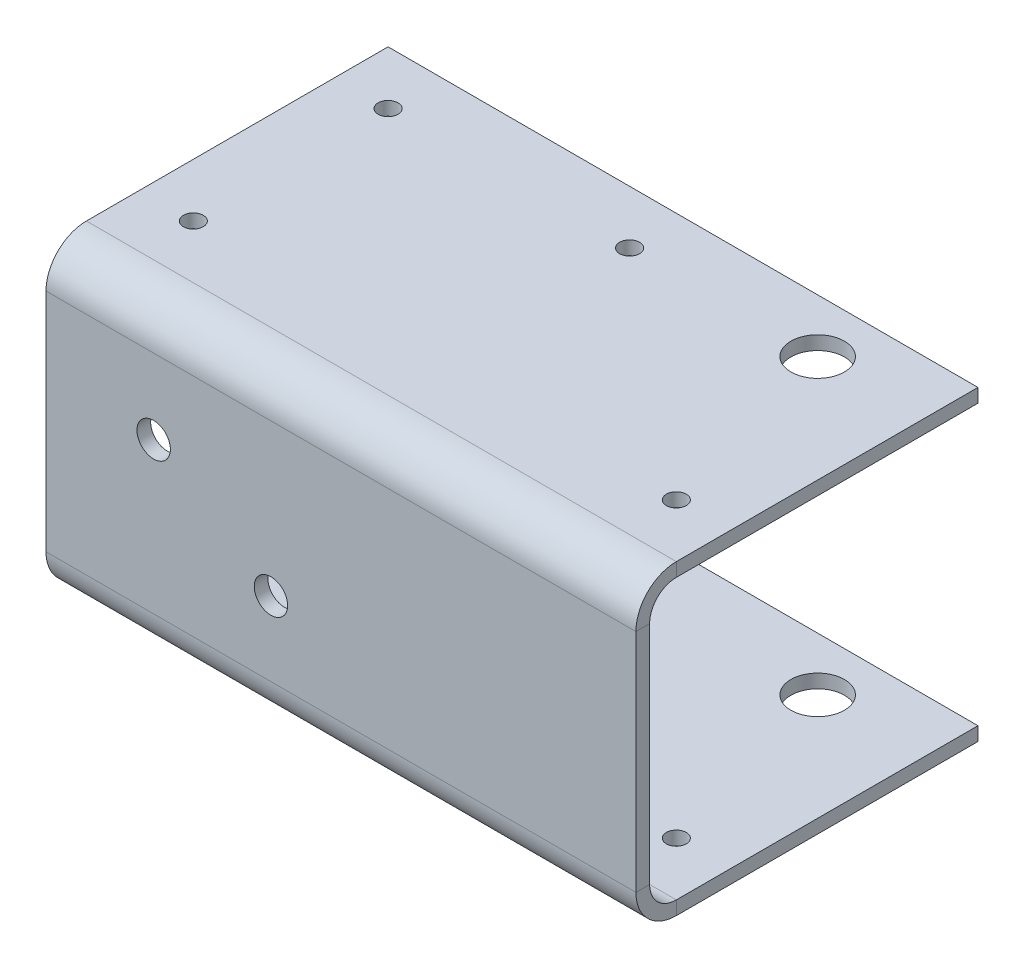
SolidWorks part; units mm, degrees
note: The reader was unsure of these and kept them because the rebuilt part matched: flange length of "Edge-Flange1".
material "6061-T6 (SS)"
ref_plane "Front Plane" through (0, 0, 0) normal (0, 0, 1) x (1, 0, 0)
ref_plane "Top Plane" through (0, 0, 0) normal (0, 1, 0) x (1, 0, 0)
ref_plane "Right Plane" through (0, 0, 0) normal (1, 0, 0) x (0, 0, -1)
sketch "Sketch1" plane through (0, 0, 0) normal (0, 0, 1) x (1, 0, 0)
  line L0 (-23.045, -12.8172) -> (5.6472, -12.8172) construction
  line L1 (5.6472, -12.8172) -> (11.9972, -12.8172) construction
  line L2 (11.9972, 3.7728) -> (11.9972, -12.8172) construction
  line L3 (5.6472, 3.7728) -> (11.9972, 3.7728) construction
  line L4 (-23.045, 3.7728) -> (5.6472, 3.7728) construction
  line L5 (-23.045, -12.8172) -> (-23.045, 3.7728) construction
  line L7 (-23.045, -12.8172) -> (5.6472, -12.8172)
  line L9 (5.6472, -12.8172) -> (11.9972, -12.8172)
  line L10 (11.9972, 3.7728) -> (11.9972, -12.8172)
  line L13 (5.6472, 3.7728) -> (11.9972, 3.7728)
  line L14 (-23.045, 3.7728) -> (5.6472, 3.7728)
  line L15 (-23.045, -12.8172) -> (-23.045, 3.7728)
base flange "Base-Flange1" sketch "Sketch1" thickness 0.8128 reverse thickness direction yes parameters "D1"=0.8128
edge flange "Edge-Flange1" sketch "Sketch13" flange profiles "Sketch13", "Sketch15" flange angle 90 flange length 20.32 flange position material outside bend radius 1.5875 thickness 0.8128 relief rectangular parameters "D6"=10, "D8"=1
bend "EdgeBend1" bend radius 1.5875 bend angle 90 parameters "D5"=1
bend "EdgeBend2" bend radius 1.5875 bend angle 90 parameters "D5"=2
sketch "Sketch13" plane through (0, 3.7728, 0) normal (0, 1, 0) x (1, 0, 0)
  line L0 (11.9972, 0) -> (-23.045, 0) construction
  line L1 (11.9972, 0) -> (-23.045, 0)
  line L2 (-23.045, 0) -> (-23.045, 19.5072)
  line L3 (-23.045, 19.5072) -> (11.9972, 19.5072)
  line L4 (11.9972, 19.5072) -> (11.9972, 0)
sketch "Sketch15" plane through (0, -12.8172, 0) normal (0, -1, 0) x (-1, 0, 0)
  line L0 (23.045, 0) -> (-11.9972, 0) construction
  line L1 (23.045, 0) -> (-11.9972, 0)
  line L2 (-11.9972, 0) -> (-11.9972, 19.5072)
  line L3 (-11.9972, 19.5072) -> (23.045, 19.5072)
  line L4 (23.045, 19.5072) -> (23.045, 0)
hole_wizard "1/8 (0.125) Diameter Hole1" positions "Sketch17" profile "Sketch16" hole size "1/8" standard "ANSI Inch" end condition through all
sketch "Sketch17" plane through (0, -13.63, 0) normal (0, -1, 0) x (-1, 0, 0)
  line L0 (-11.9972, 19.5072) -> (-11.9972, 1.5875) construction
  line L1 (23.045, 19.5072) -> (-11.9972, 19.5072) construction
  point P0 (-5.6472, 16.3322)
  dimension "D1" = 6.35
  dimension "D2" = 3.175
sketch "Sketch16" plane through (5.6472, -13.63, -16.3322) normal (1, 0, 0) x (0, 0, -1)
  line L0 (0, 0) -> (0, 18.2156)
  line L1 (0, 18.2156) -> (1.5875, 18.2156)
  line L2 (1.5875, 18.2156) -> (1.5875, 0)
  line L5 (1.5875, 0) -> (0, 0)
  line L11 (0, -6.35) -> (0, 107.95) construction
  dimension "Thru Hole Dia." = 3.175
  dimension "Thru Hole Depth" = 18.2156
hole_wizard "#56 (0.0465) Diameter Hole1" positions "Sketch19" profile "Sketch18" hole size "#56" standard "ANSI Inch" end condition through all
sketch "Sketch19" plane through (0, -13.63, 0) normal (0, -1, 0) x (-1, 0, 0)
  point P0 (5.5239, 16.3322)
  point P3 (19.87, 16.3322)
  point P6 (19.87, 4.7625)
  point P9 (-8.8222, 4.7625)
sketch "Sketch18" plane through (-5.5239, -13.63, -16.3322) normal (1, 0, 0) x (0, 0, -1)
  line L0 (0, 0) -> (0, 18.2156)
  line L1 (0, 18.2156) -> (0.5905, 18.2156)
  line L2 (0.5905, 18.2156) -> (0.5905, 0)
  line L5 (0.5905, 0) -> (0, 0)
  line L11 (0, -6.35) -> (0, 107.95) construction
  dimension "Thru Hole Dia." = 1.1811
  dimension "Thru Hole Depth" = 18.2156
hole_wizard "5/64 (0.07813) Diameter Hole1" positions "Sketch21" profile "Sketch20" hole size "5/64" standard "ANSI Inch" end condition through all
sketch "Sketch21" plane through (0, 0, 0.8128) normal (0, 0, 1) x (1, 0, 0)
  point P0 (-16.6489, -2.2697)
  point P3 (-9.6839, -6.8247)
sketch "Sketch20" plane through (-16.6489, -2.2697, 0.8128) normal (1, 0, 0) x (0, -1, 0)
  line L0 (0, 0) -> (0, 20.32)
  line L1 (0, 20.32) -> (0.9923, 20.32)
  line L2 (0.9923, 20.32) -> (0.9923, 0)
  line L5 (0.9923, 0) -> (0, 0)
  line L11 (0, -6.35) -> (0, 107.95) construction
  dimension "Thru Hole Dia." = 1.9845
  dimension "Thru Hole Depth" = 20.32
sketch "Bend-Lines1" [suppressed] plane through (0, 0, 0) normal (0, 1, 0) x (1, 0, 0)
sketch "Bounding-Box1" [suppressed] plane through (0, 0, 0) normal (0, 1, 0) x (1, 0, 0)
sheet metal parameters "Sheet-Metal1" thickness 0.8128 parameters "D1"=0.8128
flat pattern "Flat-Pattern1" [suppressed]
sketch "Bend-Lines2" plane through (0, 0, 0) normal (0, 1, 0) x (1, 0, 0)
sketch3d "Bounding-Box2" [suppressed]
  line L0 (-15.97, -8.27, 0) -> (22.42, -8.27, 0) construction
  line L1 (-15.97, 8.32, 0) -> (22.42, 8.32, 0) construction
  line L2 (-15.97, -8.27, 0) -> (-15.97, 8.32, 0) construction
  line L3 (22.42, -8.27, 0) -> (22.42, 8.32, 0) construction
sheet metal parameters "Sheet-Metal2" thickness 0.8128 parameters "D1"=0.8128
flat pattern "Flat-Pattern1"
sketch "Bend-Lines2" plane through (0, 0, 0) normal (0, 0, -1) x (-1, 0, 0)
  line L4 (-22.42, -7.931) -> (15.97, -7.931) construction
  line L5 (15.97, 7.0715) -> (-22.42, 7.0715) construction
  line L6 (-22.42, -7.931) -> (15.97, -7.931) construction
  line L7 (15.97, 7.0715) -> (-22.42, 7.0715) construction
  point P0 (15.97, 7.5263)
  point P1 (-22.42, 7.5263)
  point P2 (-22.42, -7.4763)
  point P3 (15.97, -7.4763)
sketch3d "Bounding-Box2" [suppressed]
  line L0 (-22.42, 25.785, 0) -> (-22.42, -26.6444, 0) construction
  line L1 (15.97, 25.785, 0) -> (15.97, -26.6444, 0) construction
  line L2 (-22.42, 25.785, 0) -> (15.97, 25.785, 0) construction
  line L3 (-22.42, -26.6444, 0) -> (15.97, -26.6444, 0) construction
bend of the flat pattern "Flatten-<EdgeBend1>1"
bend of the flat pattern "Flatten-<EdgeBend2>1"
sheet metal parameters "Sheet-Metal4" thickness 0.8128 parameters "D1"=0.8128
flat pattern "Flat-Pattern1"
sketch "Bend-Lines2" plane through (0, 0, 0) normal (0, 0, -1) x (-1, 0, 0)
  line L4 (-11.9972, -12.0234) -> (26.3928, -12.0234) construction
  line L5 (26.3928, 2.9791) -> (-11.9972, 2.9791) construction
  line L6 (-11.9972, -12.0234) -> (26.3928, -12.0234) construction
  line L7 (26.3928, 2.9791) -> (-11.9972, 2.9791) construction
sketch3d "Bounding-Box2" [suppressed]
  line L0 (-11.9972, 21.6925, 0) -> (-11.9972, -30.7369, 0) construction
  line L1 (26.3928, 21.6925, 0) -> (26.3928, -30.7369, 0) construction
  line L2 (-11.9972, 21.6925, 0) -> (26.3928, 21.6925, 0) construction
  line L3 (-11.9972, -30.7369, 0) -> (26.3928, -30.7369, 0) construction
bend of the flat pattern "Flatten-<EdgeBend1>1"
bend of the flat pattern "Flatten-<EdgeBend2>1"
sheet metal parameters "Sheet-Metal5" thickness 0.8128 parameters "D1"=0.8128
flat pattern "Flat-Pattern1"
sketch "Bend-Lines2" plane through (0, 0, 0) normal (0, 0, -1) x (-1, 0, 0)
  line L4 (-11.9972, -12.0234) -> (26.3928, -12.0234) construction
  line L5 (26.3928, 2.9791) -> (-11.9972, 2.9791) construction
  line L6 (-11.9972, -12.0234) -> (26.3928, -12.0234) construction
  line L7 (26.3928, 2.9791) -> (-11.9972, 2.9791) construction
sketch3d "Bounding-Box2" [suppressed]
  line L0 (-11.9972, 21.6925, 0) -> (-11.9972, -30.7369, 0) construction
  line L1 (26.3928, 21.6925, 0) -> (26.3928, -30.7369, 0) construction
  line L2 (-11.9972, 21.6925, 0) -> (26.3928, 21.6925, 0) construction
  line L3 (-11.9972, -30.7369, 0) -> (26.3928, -30.7369, 0) construction
bend of the flat pattern "Flatten-<EdgeBend1>1"
bend of the flat pattern "Flatten-<EdgeBend2>1"
sheet metal parameters "Sheet-Metal6" thickness 0.8128 parameters "D1"=0.8128
flat pattern "Flat-Pattern1"
sketch "Bend-Lines2" plane through (0, 0, 0) normal (0, 0, -1) x (-1, 0, 0)
  line L4 (-11.9972, -12.0234) -> (23.045, -12.0234) construction
  line L5 (23.045, 2.9791) -> (-11.9972, 2.9791) construction
  line L6 (-11.9972, -12.0234) -> (23.045, -12.0234) construction
  line L7 (23.045, 2.9791) -> (-11.9972, 2.9791) construction
sketch3d "Bounding-Box2" [suppressed]
  line L0 (-11.9972, 21.6925, 0) -> (-11.9972, -30.7369, 0) construction
  line L1 (23.045, 21.6925, 0) -> (23.045, -30.7369, 0) construction
  line L2 (-11.9972, 21.6925, 0) -> (23.045, 21.6925, 0) construction
  line L3 (-11.9972, -30.7369, 0) -> (23.045, -30.7369, 0) construction
bend of the flat pattern "Flatten-<EdgeBend1>1"
bend of the flat pattern "Flatten-<EdgeBend2>1"
